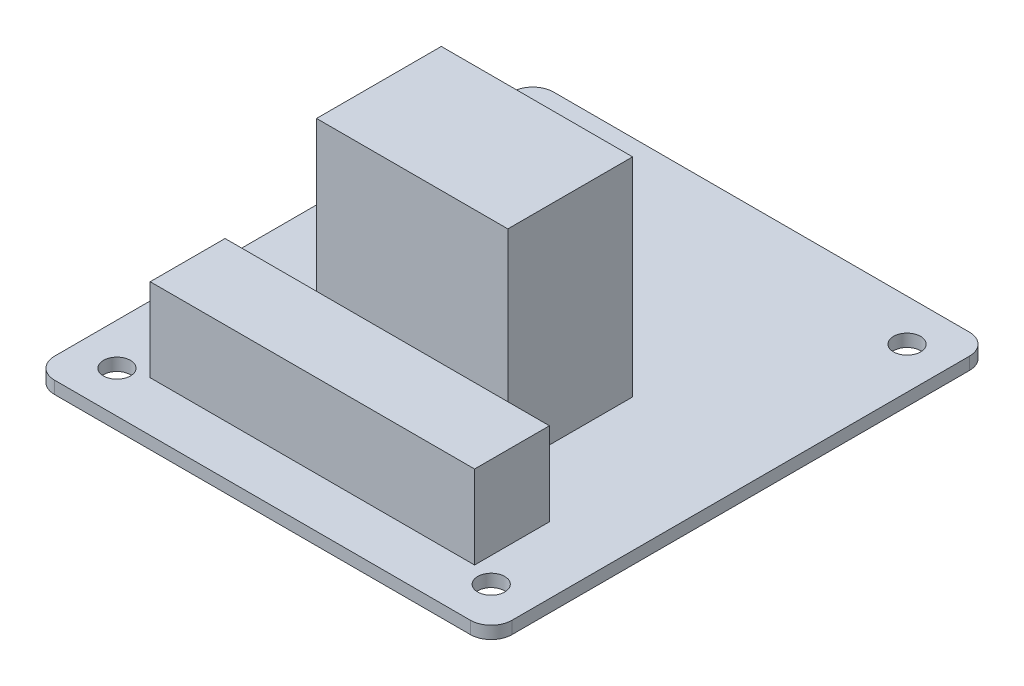
SolidWorks part; units mm, degrees
ref_plane "Front Plane" through (0, 0, 0) normal (0, 0, 1) x (1, 0, 0)
ref_plane "Top Plane" through (0, 0, 0) normal (0, 1, 0) x (1, 0, 0)
ref_plane "Right Plane" through (0, 0, 0) normal (1, 0, 0) x (0, 0, -1)
sketch "Sketch1" plane through (0, 0, 0) normal (0, 1, 0) x (1, 0, 0)
  line L0 (27.5, 0) -> (27.5, 60) construction
  line L1 (2.5, 0) -> (52.5, 0)
  line L2 (0, 2.5) -> (0, 57.5)
  line L3 (2.5, 60) -> (52.5, 60)
  line L4 (55, 2.5) -> (55, 57.5)
  line L5 (8, 15) -> (47, 15)
  line L6 (8, 15) -> (8, 6)
  line L7 (8, 6) -> (47, 6)
  line L8 (47, 15) -> (47, 6)
  line L9 (0, 30) -> (55, 30) construction
  line L11 (16, 18) -> (39, 18)
  line L12 (16, 18) -> (16, 33)
  line L13 (16, 33) -> (39, 33)
  line L14 (39, 18) -> (39, 33)
  line L15 (16, 18) -> (39, 33) construction
  line L16 (16, 33) -> (39, 18) construction
  circle A0 centre (5, 5) radius 1.625
  circle A1 centre (50, 5) radius 1.625
  circle A2 centre (50, 55) radius 1.625
  circle A3 centre (5, 55) radius 1.625
  arc A4 (52.5, 60) -> (55, 57.5) centre (52.5, 57.5) cw
  arc A5 (52.5, 0) -> (55, 2.5) centre (52.5, 2.5) ccw
  arc A6 (2.5, 0) -> (0, 2.5) centre (2.5, 2.5) cw
  arc A7 (0, 57.5) -> (2.5, 60) centre (2.5, 57.5) cw
  point P22 (27.5, 6)
  point P23 (27.5, 25.5)
  point P30 (55, 60)
  point P33 (55, 0)
  point P36 (0, 0)
  dimension "D3" = 3.25
  dimension "D12" = 2.5
  dimension "D1" = 55
  dimension "D2" = 60
  dimension "D4" = 45
  dimension "D5" = 5
  dimension "D6" = 9
  dimension "D7" = 39
  dimension "D8" = 6
  dimension "D9" = 15
  dimension "D10" = 23
  dimension "D11" = 3
extrude "Boss-Extrude1" add sketch "Sketch1" along normal blind 1.5 contours A7 L2 A6 L1 A5 L4 A4 L3 A1 A0 L14 L11 L12 L13 L5 L8 L7 L6 A2 A3 | L11 L14 L13 L12 | L8 L5 L6 L7 region at (27.5, 0, -33.2731) region at (27.5, 0, -10.5) region at (27.5, 0, -25.5)
extrude "Boss-Extrude2" add sketch "Sketch1<4>" along normal blind 10 from surface separate body contours L8 L5 L6 L7 region at (27.5, 0, -10.5) starting at face at (27.5, 1.5, -30)
sketch "Sketch1<4>" plane through (0, 0, 0) normal (0, 1, 0) x (1, 0, 0) same geometry as "Sketch1"
extrude "Boss-Extrude3" add sketch "Sketch1<5>" along normal blind 25 from surface separate body contours L11 L14 L13 L12 region at (27.5, 0, -25.5) starting at face at (27.5, 1.5, -30)
sketch "Sketch1<5>" plane through (0, 0, 0) normal (0, 1, 0) x (1, 0, 0) same geometry as "Sketch1"
